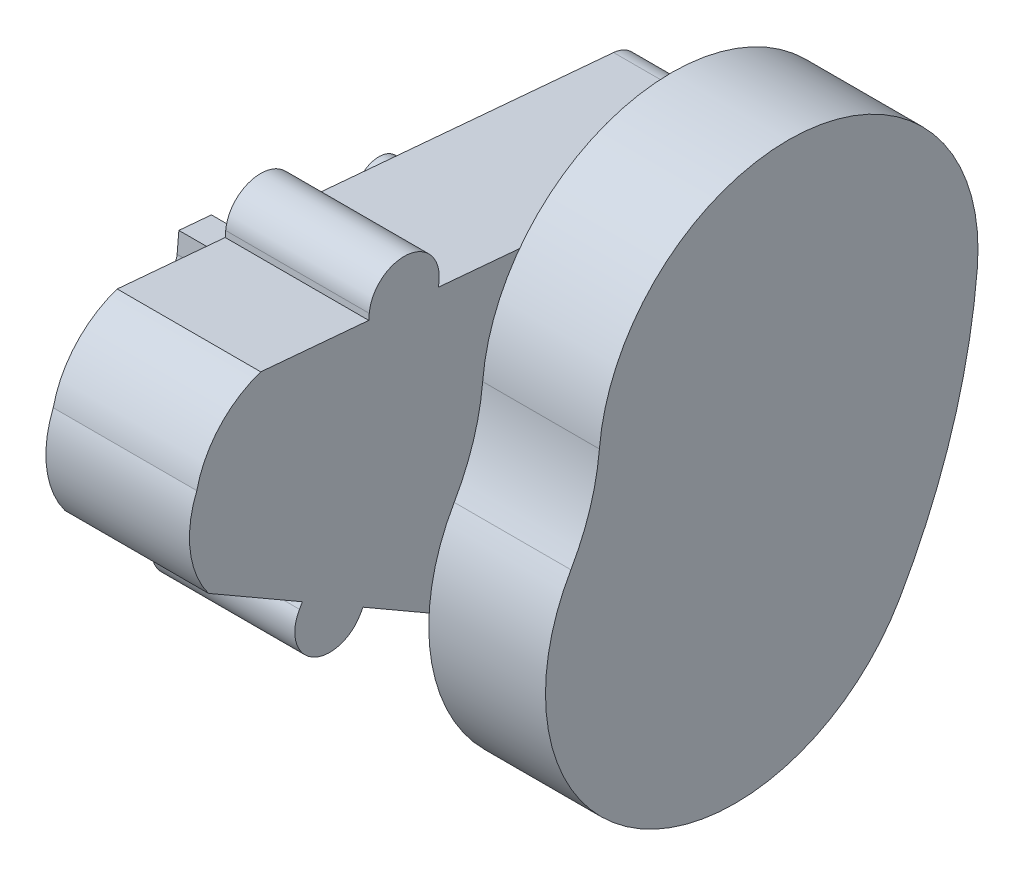
SolidWorks part; units mm, degrees
ref_plane "Front Plane" through (0, 0, 0) normal (0, 0, 1) x (1, 0, 0)
ref_plane "Top Plane" through (0, 0, 0) normal (0, 1, 0) x (1, 0, 0)
ref_plane "Right Plane" through (0, 0, 0) normal (1, 0, 0) x (0, 0, -1)
sketch "Sketch1" plane through (0, 0, 0) normal (1, 0, 0) x (0, 0, -1)
  line L0 (3.1052, 15.25) -> (16, 14.1219) construction
  line L1 (3.1052, 15.25) -> (16, 14.1219) construction
  line L2 (-0.2321, -17.5002) -> (-13.4374, -9.8761) construction
  line L3 (-0.2321, -17.5002) -> (-13.4374, -9.8761) construction
sketch "Sketch2"
sketch_block_instance "Block2-1"
sketch_block "Block2"
sketch "Sketch5" plane through (21.6, 0, 0) normal (1, 0, 0) x (0, 0, -1)
  line L1 (-0.2321, -17.5002) -> (-13.4374, -9.8761) construction
  line L2 (3.1052, 15.25) -> (16, 14.1219) construction
  line B0 (7.625, 13.2069) -> (-7.625, -13.2069)
  line B1 (8.4666, -22.4974) -> (7.9666, -23.3634)
  line B2 (18.3589, -29.3634) -> (18.8589, -28.4974)
  line B3 (18.8589, -28.4974) -> (66.3162, -55.8969)
  line B4 (73.1464, -54.0668) -> (83.3964, -36.3132)
  line B5 (81.5662, -29.4831) -> (34.1089, -2.0836)
  line B6 (34.1089, -2.0836) -> (34.6089, -1.2176)
  line B7 (24.2166, 4.7824) -> (23.7166, 3.9164)
  line B8 (23.7166, 3.9164) -> (7.625, 13.2069)
  line B9 (-7.625, -13.2069) -> (8.4666, -22.4974)
  circle B10 centre (60.6218, -35) radius 1.25
  arc B11 (7.9666, -23.3634) -> (18.3589, -29.3634) centre (13.1628, -26.3634) ccw
  arc B12 (66.3162, -55.8969) -> (73.1464, -54.0668) centre (68.8162, -51.5668) ccw
  arc B13 (83.3964, -36.3132) -> (81.5662, -29.4831) centre (79.0662, -33.8132) ccw
  arc B14 (34.6089, -1.2176) -> (24.2166, 4.7824) centre (29.4128, 1.7824) ccw
  arc B15 (7.625, 13.2069) -> (-7.625, -13.2069) centre (5.7401, -3.3141) ccw
  line B16 (1.3291, 15.192) -> (-1.3291, -15.192)
  line B17 (17.1812, -16.8114) -> (17.094, -17.8076)
  line B18 (29.1355, -17.8573) -> (83.726, -22.6333)
  line B19 (89.1427, -18.0881) -> (90.9294, 2.3339)
  line B20 (86.3842, 7.7506) -> (31.7938, 12.5267)
  line B21 (31.7938, 12.5267) -> (31.8809, 13.5229)
  line B22 (19.9266, 14.5687) -> (19.8394, 13.5725)
  line B23 (19.8394, 13.5725) -> (1.3291, 15.192)
  line B24 (-1.3291, -15.192) -> (17.1812, -16.8114)
  circle B25 centre (69.7336, -6.1009) radius 1.25
  arc B26 (17.094, -17.8076) -> (29.0483, -18.8535) centre (23.0712, -18.3305) ccw
  arc B27 (83.726, -22.6333) -> (89.1427, -18.0881) centre (84.1618, -17.6524) ccw
  arc B28 (90.9294, 2.3339) -> (86.3842, 7.7506) centre (85.9484, 2.7696) ccw
  arc B29 (31.8809, 13.5229) -> (19.9266, 14.5687) centre (25.9037, 14.0458) ccw
  arc B30 (1.3291, 15.192) -> (-1.3291, -15.192) centre (6.6029, -0.5777) ccw
sketch_block_instance "Block2-2"
sketch_block_instance "Block2-3"
sketch "Sketch7" plane through (21.6, 0, 0) normal (1, 0, 0) x (0, 0, -1)
  line L0 (-7.625, -13.2069) -> (8.4666, -22.4974) construction
  line L1 (8.4666, -22.4974) -> (7.9666, -23.3634) construction
  line L2 (18.3589, -29.3634) -> (18.8589, -28.4974) construction
  line L3 (18.8589, -28.4974) -> (66.3162, -55.8969) construction
  line L4 (-7.625, -13.2069) -> (8.4666, -22.4974)
  line L5 (8.4666, -22.4974) -> (7.9666, -23.3634)
  line L6 (18.3589, -29.3634) -> (18.8589, -28.4974)
  line L7 (18.8589, -28.4974) -> (66.3162, -55.8969)
  line L8 (86.3842, 7.7506) -> (31.7938, 12.5267) construction
  line L9 (31.7938, 12.5267) -> (31.8809, 13.5229) construction
  line L10 (19.9266, 14.5687) -> (19.8394, 13.5725) construction
  line L11 (19.8394, 13.5725) -> (1.3291, 15.192) construction
  line L12 (86.3842, 7.7506) -> (31.7938, 12.5267)
  line L13 (31.7938, 12.5267) -> (31.8809, 13.5229)
  line L14 (19.9266, 14.5687) -> (19.8394, 13.5725)
  line L15 (19.8394, 13.5725) -> (1.3291, 15.192)
  arc A1 (72.4316, -55.0206) -> (90.891, 3.5252) centre (0, 0) ccw
  arc A2 (7.625, 13.2069) -> (-7.625, -13.2069) centre (5.7401, -3.3141) ccw construction
  arc A3 (7.9666, -23.3634) -> (18.3589, -29.3634) centre (13.1628, -26.3634) ccw construction
  arc A4 (66.3162, -55.8969) -> (73.1464, -54.0668) centre (68.8162, -51.5668) ccw construction
  arc A5 (-9.6279, 3.0357) -> (-7.625, -13.2069) centre (5.7401, -3.3141) ccw
  arc A6 (7.9666, -23.3634) -> (18.3589, -29.3634) centre (13.1628, -26.3634) ccw
  arc A7 (66.3162, -55.8969) -> (72.4316, -55.0206) centre (68.8162, -51.5668) ccw
  arc A8 (90.9294, 2.3339) -> (86.3842, 7.7506) centre (85.9484, 2.7696) ccw construction
  arc A9 (31.8809, 13.5229) -> (19.9266, 14.5687) centre (25.9037, 14.0458) ccw construction
  arc A10 (1.3291, 15.192) -> (-1.3291, -15.192) centre (6.6029, -0.5777) ccw construction
  arc A11 (90.891, 3.5252) -> (86.3842, 7.7506) centre (85.9484, 2.7696) ccw
  arc A12 (31.8809, 13.5229) -> (19.9266, 14.5687) centre (25.9037, 14.0458) ccw
  arc A13 (1.3291, 15.192) -> (-9.6279, 3.0357) centre (6.6029, -0.5777) ccw
extrude "Boss-Extrude2" add sketch "Sketch7" against normal up to surface (24.6 mm away)
sketch "Sketch8" plane through (-3, 0, 0) normal (-1, 0, 0) x (0, 0, 1)
  line L0 (-19.8394, 13.5725) -> (-1.3291, 15.192) construction
  line B0 (0, 0) -> (-50.1539, 4.3955) construction
  line B1 (0, 0) -> (-48.6287, -13.0379) construction
  line B2 (0, 0) -> (-49.3913, -4.3212) construction
  line B3 (-49.3913, -4.3212) -> (-50.1539, 4.3955) construction
  circle B4 centre (-50.1539, 4.3955) radius 4
  circle B5 centre (-48.6287, -13.0379) radius 4
sketch_block_instance "Block4-1"
sketch_block "Block4"
sketch "Sketch9" plane through (-3, 0, 0) normal (-1, 0, 0) x (0, 0, 1)
  line L3 (-81.5662, -29.4831) -> (-34.1089, -2.0836) construction
  line B0 (0, 0) -> (-47.3125, -17.2123) construction
  line B1 (0, 0) -> (-38.5625, -32.3677) construction
  line B2 (0, 0) -> (-42.9375, -24.79) construction
  line B3 (-42.9375, -24.79) -> (-47.3125, -17.2123) construction
  circle B4 centre (-47.3125, -17.2123) radius 4
  circle B5 centre (-38.5625, -32.3677) radius 4
sketch_block_instance "Block4-2"
sketch "Sketch10" plane through (-3, 0, 0) normal (-1, 0, 0) x (0, 0, 1)
  arc A0 (-54.1387, 4.7447) -> (-41.6263, -34.9393) centre (0, 0) ccw
  circle A1 centre (-50.1539, 4.3955) radius 4 construction
  circle A2 centre (-38.5625, -32.3677) radius 4 construction
  arc A3 (-41.6263, -34.9393) -> (-35.4987, -29.7961) centre (-38.5625, -32.3677) ccw
  arc A4 (-46.1692, 4.0463) -> (-54.1387, 4.7447) centre (-50.1539, 4.3955) ccw
  arc A5 (-35.4987, -29.7961) -> (-46.1692, 4.0463) centre (0, 0) cw
  circle A6 centre (-48.6287, -13.0379) radius 4 construction
extrude "Boss-Extrude3" add sketch "Sketch10" along normal up to surface (4 mm away)
sketch "Sketch11" plane through (-3, 0, 0) normal (-1, 0, 0) x (0, 0, 1)
  line L0 (-81.5662, -29.4831) -> (-34.1089, -2.0836) construction
  line L24 (-1.3291, 15.192) -> (-19.8394, 13.5725) construction
  line B0 (-28.1501, -9.615) -> (-31.6368, -9.9201)
  line B1 (-25.8596, -12.8477) -> (-25.9834, -11.4331)
  line B2 (-20.281, -12.3596) -> (-25.8596, -12.8477)
  line B3 (-20.579, -8.9526) -> (-20.281, -12.3596)
  line B4 (-14.7762, -6.4373) -> (-18.761, -6.7859)
  line B5 (-15.6477, 3.5246) -> (-14.7762, -6.4373)
  line B6 (-19.6325, 3.176) -> (-15.6477, 3.5246)
  line B7 (-22.0973, 8.4011) -> (-21.7992, 4.9941)
  line B8 (-27.676, 7.913) -> (-22.0973, 8.4011)
  line B9 (-27.5522, 6.4984) -> (-27.676, 7.913)
  line B10 (-32.857, 4.0266) -> (-29.3703, 4.3317)
  line B11 (-31.6368, -9.9201) -> (-32.857, 4.0266)
  line B12 (-15.2228, -1.3318) -> (0, 0)
  arc B13 (-25.9834, -11.4331) -> (-28.1501, -9.615) centre (-27.9758, -11.6074) ccw
  arc B14 (-18.761, -6.7859) -> (-20.579, -8.9526) centre (-18.5866, -8.7783) ccw
  arc B15 (-21.7992, 4.9941) -> (-19.6325, 3.176) centre (-19.8068, 5.1684) ccw
  arc B16 (-29.3703, 4.3317) -> (-27.5522, 6.4984) centre (-29.5446, 6.3241) ccw
  line B17 (-21.4492, -20.6109) -> (-24.4803, -22.3609)
  line B18 (-18.0071, -22.5727) -> (-18.7171, -21.343)
  line B19 (-13.1574, -19.7727) -> (-18.0071, -22.5727)
  line B20 (-14.8674, -16.8109) -> (-13.1574, -19.7727)
  line B21 (-10.6712, -12.0789) -> (-14.1353, -14.0789)
  line B22 (-15.6712, -3.4186) -> (-10.6712, -12.0789)
  line B23 (-19.1353, -5.4186) -> (-15.6712, -3.4186)
  line B24 (-23.5774, -1.7248) -> (-21.8674, -4.6866)
  line B25 (-28.4271, -4.5248) -> (-23.5774, -1.7248)
  line B26 (-31.4803, -10.2366) -> (-28.4492, -8.4866)
  line B27 (-24.4803, -22.3609) -> (-31.4803, -10.2366)
  line B28 (-13.2337, -7.6405) -> (0, 0)
  arc B29 (-18.7171, -21.343) -> (-21.4492, -20.6109) centre (-20.4492, -22.343) ccw
  arc B30 (-14.1353, -14.0789) -> (-14.8674, -16.8109) centre (-13.1353, -15.8109) ccw
sketch_block_instance "Block7-1"
sketch_block "Block7"
sketch_block_instance "Block7-2"
sketch "Sketch13" plane through (-3, 0, 0) normal (-1, 0, 0) x (0, 0, 1)
  line L0 (-7.625, 13.2069) -> (7.625, -13.2069) construction
  line L1 (-10.6712, -12.0789) -> (-14.1353, -14.0789) construction
  line L2 (-14.8674, -16.8109) -> (-13.1574, -19.7727) construction
  line L3 (-13.1574, -19.7727) -> (-18.0071, -22.5727) construction
  line L4 (-18.0071, -22.5727) -> (-18.7171, -21.343) construction
  line L5 (-21.4492, -20.6109) -> (-24.4803, -22.3609) construction
  line L6 (-19.6325, 3.176) -> (-15.6477, 3.5246) construction
  line L7 (-22.0973, 8.4011) -> (-21.7992, 4.9941) construction
  line L8 (-27.676, 7.913) -> (-22.0973, 8.4011) construction
  line L9 (-27.5522, 6.4984) -> (-27.676, 7.913) construction
  line L10 (-32.857, 4.0266) -> (-29.3703, 4.3317) construction
  line L11 (-10.6712, -12.0789) -> (-14.1353, -14.0789)
  line L12 (-14.8674, -16.8109) -> (-13.1574, -19.7727)
  line L13 (-13.1574, -19.7727) -> (-18.0071, -22.5727)
  line L14 (-18.0071, -22.5727) -> (-18.7171, -21.343)
  line L15 (-21.4492, -20.6109) -> (-24.4803, -22.3609)
  line L16 (-19.6325, 3.176) -> (-15.6477, 3.5246)
  line L17 (-22.0973, 8.4011) -> (-21.7992, 4.9941)
  line L18 (-27.676, 7.913) -> (-22.0973, 8.4011)
  line L19 (-27.5522, 6.4984) -> (-27.676, 7.913)
  line L20 (-32.857, 4.0266) -> (-29.3703, 4.3317)
  line L21 (-15.6477, 3.5246) -> (-14.7762, -6.4373) construction
  arc A0 (-32.857, 4.0266) -> (-24.4803, -22.3609) centre (0.0324, -0.056) ccw
  arc A1 (-14.1353, -14.0789) -> (-14.8674, -16.8109) centre (-13.1353, -15.8109) ccw construction
  arc A2 (-18.7171, -21.343) -> (-21.4492, -20.6109) centre (-20.4492, -22.343) ccw construction
  arc A3 (-21.7992, 4.9941) -> (-19.6325, 3.176) centre (-19.8068, 5.1684) ccw construction
  arc A4 (-29.3703, 4.3317) -> (-27.5522, 6.4984) centre (-29.5446, 6.3241) ccw construction
  arc A5 (-14.1353, -14.0789) -> (-14.8674, -16.8109) centre (-13.1353, -15.8109) ccw
  arc A6 (-18.7171, -21.343) -> (-21.4492, -20.6109) centre (-20.4492, -22.343) ccw
  arc A7 (-21.7992, 4.9941) -> (-19.6325, 3.176) centre (-19.8068, 5.1684) ccw
  arc A8 (-29.3703, 4.3317) -> (-27.5522, 6.4984) centre (-29.5446, 6.3241) ccw
  arc A10 (-10.6712, -12.0789) -> (-15.6477, 3.5246) centre (21.4898, 6.7737) cw
extrude "Boss-Extrude4" add sketch "Sketch13" along normal up to surface (10.2 mm away)
sketch "Sketch14" plane through (43.6, 0, 0) normal (1, 0, 0) x (0, 0, -1)
  line L0 (0, 0) -> (37.3573, -3.2683) construction
  line L1 (19.8394, 13.5725) -> (1.3291, 15.192) construction
  line L2 (0, 0) -> (32.476, -18.75) construction
  line L3 (81.5662, -29.4831) -> (34.1089, -2.0836) construction
  arc A0 (102.11, -8.9335) -> (37.3573, -3.2683) centre (69.7336, -6.1009) ccw
  circle A1 centre (69.7336, -6.1009) radius 32.5 construction
  arc A2 (32.476, -18.75) -> (88.7676, -51.25) centre (60.6218, -35) ccw
  arc A3 (88.7676, -51.25) -> (102.11, -8.9335) centre (0, 0) ccw
  arc A4 (32.476, -18.75) -> (37.3573, -3.2683) centre (0, 0) ccw
extrude "Boss-Extrude5" add sketch "Sketch14" against normal up to surface (20 mm away) separate body
